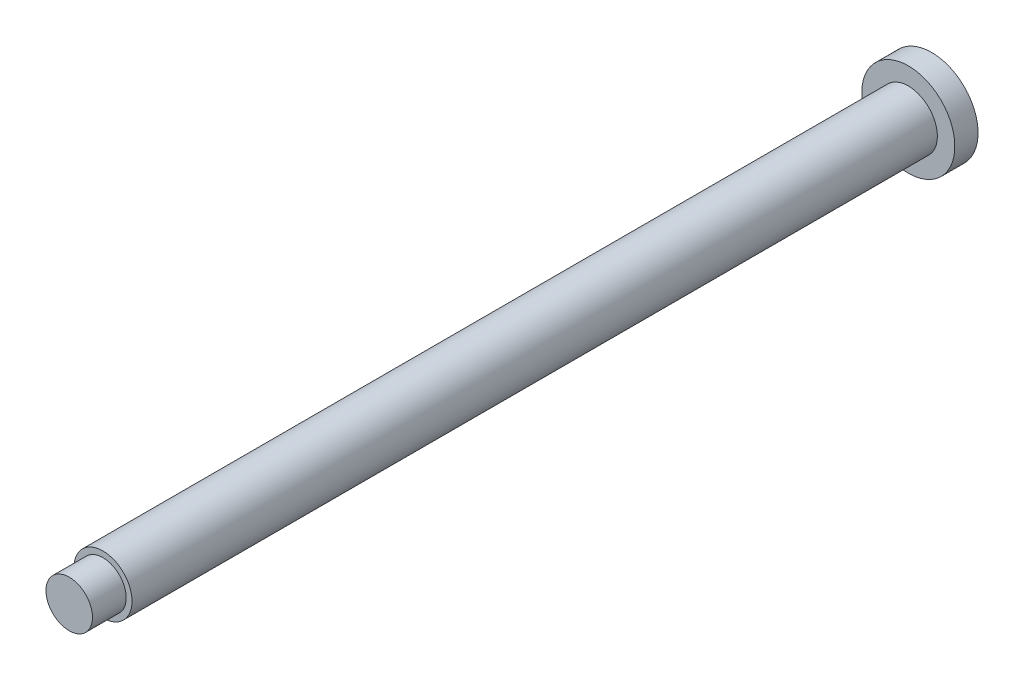
SolidWorks part; units mm, degrees
ref_plane "Front Plane" through (0, 0, 0) normal (1, 0, 0) x (0, 1, 0)
ref_plane "Top Plane" through (0, 0, 0) normal (0, 0, 1) x (0, 1, 0)
ref_plane "Right Plane" through (0, 0, 0) normal (0, 1, 0) x (-1, 0, 0)
sketch "Sketch1" plane through (0, 0, 0) normal (0, 0, 1) x (0, 1, 0)
  circle A0 centre (0, 0) radius 2.5
extrude "Boss-Extrude1" add sketch "Sketch1" along normal blind 69.25 contours A0
sketch "Sketch2" plane through (0, 0, 0) normal (0, 0, -1) x (1, 0, 0)
  circle A0 centre (0, 0) radius 4
extrude "Boss-Extrude2" add sketch "Sketch2" along normal blind 2
sketch "Sketch3" plane through (0, 0, -2) normal (0, 0, -1) x (1, 0, 0)
  circle A0 centre (0, 0) radius 2.05
extrude "Cut-Extrude1" cut sketch "Sketch3" against normal blind 3
sketch "Sketch4" plane through (0, 0, 69.25) normal (0, 0, 1) x (1, 0, 0)
  circle A0 centre (0, 0) radius 2
extrude "Boss-Extrude3" add sketch "Sketch4" along normal blind 2.9
